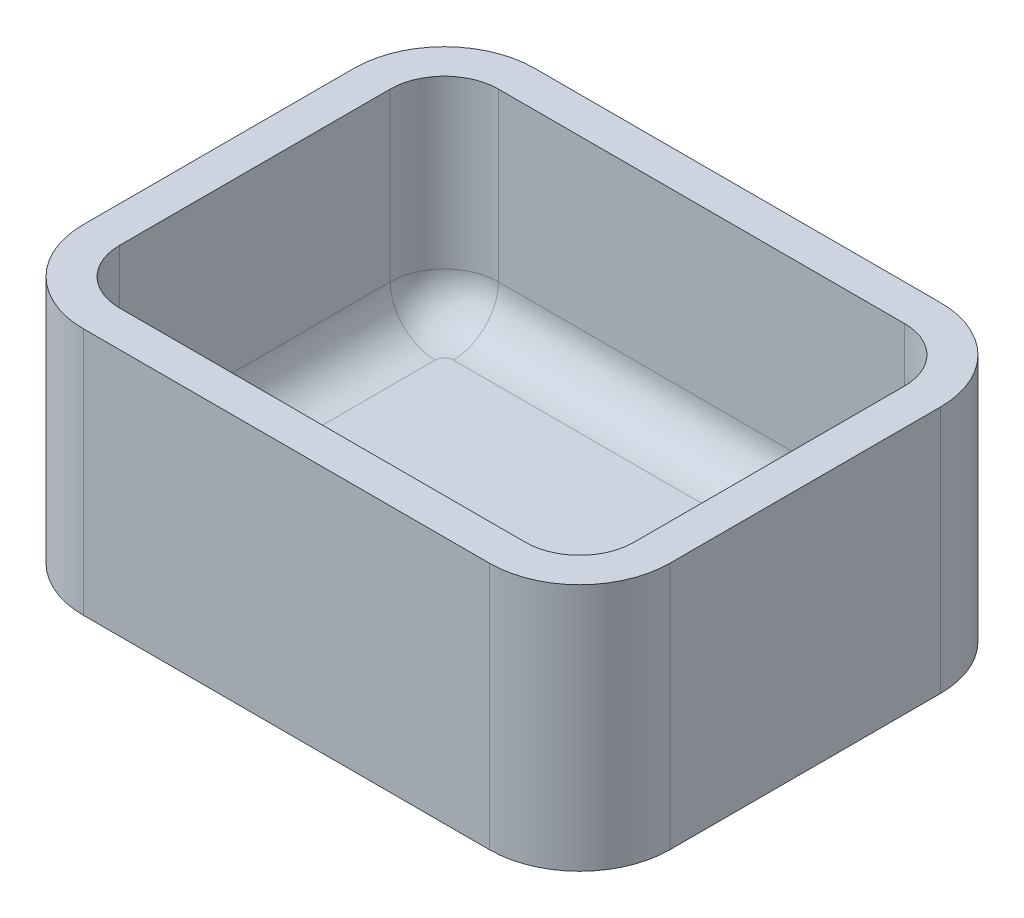
SolidWorks part; units mm, degrees
ref_plane "Plan de face" through (0, 0, 0) normal (0, 0, 1) x (1, 0, 0)
ref_plane "Plan de dessus" through (0, 0, 0) normal (0, 1, 0) x (1, 0, 0)
ref_plane "Plan de droite" through (0, 0, 0) normal (1, 0, 0) x (0, 0, -1)
sketch "Esquisse4" plane through (0, 0, 0) normal (0, 1, 0) x (1, 0, 0)
  line L1 (-52.2281, 66.2297) -> (77.7719, 66.2297)
  line L2 (-52.2281, 66.2297) -> (-52.2281, -33.7703)
  line L3 (-52.2281, -33.7703) -> (77.7719, -33.7703)
  line L4 (77.7719, 66.2297) -> (77.7719, -33.7703)
  dimension "D1" = 100
  dimension "D2" = 130
extrude "Boss.-Extru.4" add sketch "Esquisse4" along normal blind 55
ref_plane "Plan1" through (12.7719, 0, 0) normal (-1, 0, 0) x (0, 0, 1)
ref_plane "Plan2" through (0, 0, -16.2297) normal (0, 0, 1) x (1, 0, 0)
ref_axis "Axe1" through (12.7719, 110.2243, -16.2297) along (0, -1, 0)
fillet "Congé5" radius 20 4 edges at (77.7719, 27.5, 33.7703) (77.7719, 27.5, -66.2297) (-52.2281, 27.5, 33.7703) (-52.2281, 27.5, -66.2297)
sketch "Esquisse5" plane through (0, 55, 0) normal (0, 1, 0) x (1, 0, 0)
  line L24 (57.7719, 58.2297) -> (-32.2281, 58.2297)
  line L25 (69.7719, -13.7703) -> (69.7719, 46.2297)
  line L26 (-32.2281, -25.7703) -> (57.7719, -25.7703)
  line L27 (-44.2281, 46.2297) -> (-44.2281, -13.7703)
  line L28 (57.7719, 58.2297) -> (-32.2281, 58.2297)
  line L29 (69.7719, -13.7703) -> (69.7719, 46.2297)
  line L30 (-32.2281, -25.7703) -> (57.7719, -25.7703)
  line L31 (-44.2281, 46.2297) -> (-44.2281, -13.7703)
  arc A23 (69.7719, 46.2297) -> (57.7719, 58.2297) centre (57.7719, 46.2297) ccw
  arc A24 (57.7719, -25.7703) -> (69.7719, -13.7703) centre (57.7719, -13.7703) ccw
  arc A25 (-44.2281, -13.7703) -> (-32.2281, -25.7703) centre (-32.2281, -13.7703) ccw
  arc A26 (-32.2281, 58.2297) -> (-44.2281, 46.2297) centre (-32.2281, 46.2297) ccw
  arc A27 (69.7719, 46.2297) -> (57.7719, 58.2297) centre (57.7719, 46.2297) ccw
  arc A28 (57.7719, -25.7703) -> (69.7719, -13.7703) centre (57.7719, -13.7703) ccw
  arc A29 (-44.2281, -13.7703) -> (-32.2281, -25.7703) centre (-32.2281, -13.7703) ccw
  arc A30 (-32.2281, 58.2297) -> (-44.2281, 46.2297) centre (-32.2281, 46.2297) ccw
  dimension "D2" = 8
extrude "Enlèv. mat.-Extru.1" cut sketch "Esquisse5" against normal blind 47
fillet "Congé6" radius 10 8 edges at (66.2572, 8, -54.715) (69.7719, 8, -16.2297) (66.2572, 8, 22.2556) (12.7719, 8, 25.7703) (-40.7133, 8, 22.2556) (-44.2281, 8, -16.2297) (-40.7133, 8, -54.715) (12.7719, 8, -58.2297) type face fillet first side face at (12.7719, 31.5, 25.7703) first side face at (65.0146, 31.5, 21.0129) first side face at (69.7719, 31.5, -16.2297) first side face at (65.0146, 31.5, -53.4724) first side face at (-39.4707, 31.5, 21.0129) first side face at (-44.2281, 31.5, -16.2297) first side face at (-39.4707, 31.5, -53.4724) first side face at (12.7719, 31.5, -58.2297) second side face at (12.7719, 8, -16.2297) conic radius 10
